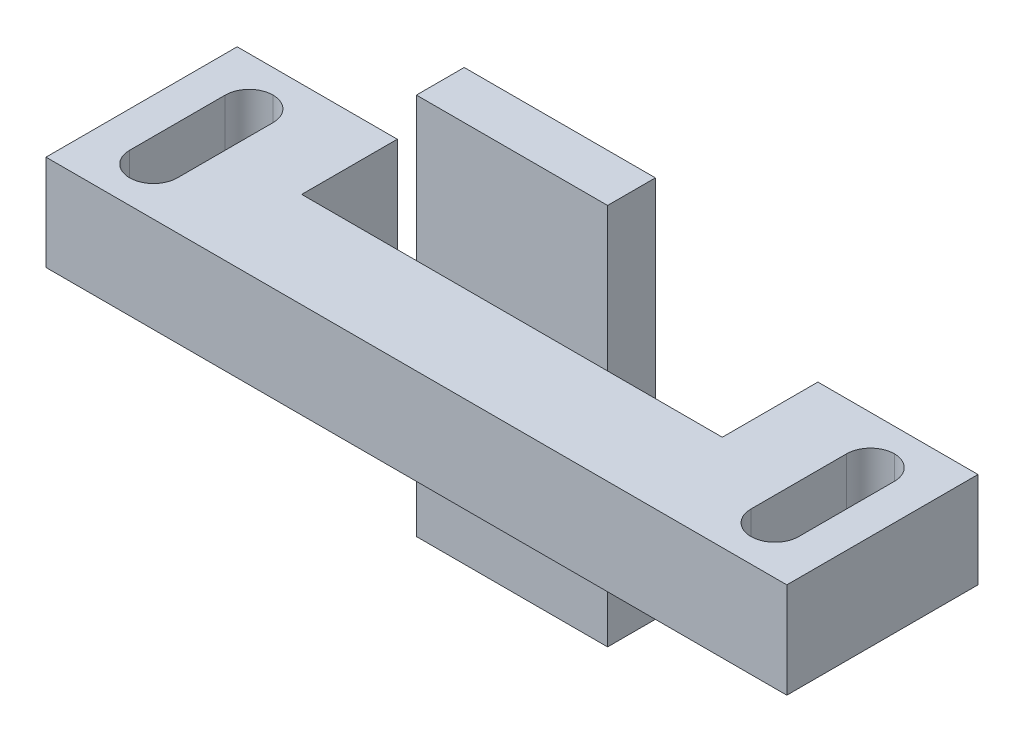
SolidWorks part; units mm, degrees
material "6061 Alloy"
ref_plane "Front Plane" through (0, 0, 0) normal (0, 0, 1) x (1, 0, 0)
ref_plane "Top Plane" through (0, 0, 0) normal (0, 1, 0) x (1, 0, 0)
ref_plane "Right Plane" through (0, 0, 0) normal (1, 0, 0) x (0, 0, -1)
sketch "Sketch1" plane through (0, 0, 0) normal (0, 0, 1) x (1, 0, 0)
  line L1 (-49.2125, 6.35) -> (49.2125, 6.35)
  line L2 (-49.2125, 6.35) -> (-49.2125, -6.35)
  line L3 (-49.2125, -6.35) -> (49.2125, -6.35)
  line L4 (49.2125, 6.35) -> (49.2125, -6.35)
  dimension "D1" = 49.2125
  dimension "D2" = 49.2125
  dimension "D3" = 6.35
  dimension "D4" = 6.35
extrude "Boss-Extrude1" add sketch "Sketch1" along normal mid plane 25.4
sketch "Sketch2" plane through (0, 6.35, 0) normal (0, 1, 0) x (1, 0, 0)
  line L1 (-44.45, 9.525) -> (-38.1, 9.525)
  line L2 (-44.45, 9.525) -> (-44.45, -9.525)
  line L3 (-44.45, -9.525) -> (-38.1, -9.525)
  line L4 (-38.1, 9.525) -> (-38.1, -9.525)
  line L5 (49.2125, 12.7) -> (-49.2125, 12.7) construction
  line L6 (49.2125, -12.7) -> (-49.2125, -12.7) construction
  dimension "D1" = 38.1
  dimension "D2" = 6.35
  dimension "D3" = 3.175
  dimension "D4" = 3.175
extrude "Cut-Extrude1" cut sketch "Sketch2" against normal up to next
fillet "Fillet1" radius 3.175 1 edges at (-44.45, 0, -9.525) type face fillet first side face at (-44.45, 0, 0) second side face at (-41.275, 0, -9.525)
fillet "Fillet2" radius 3.175 1 edges at (-38.1, 0, -9.525) type face fillet first side face at (-39.6875, 0, -9.525) second side face at (-38.1, 0, 0)
fillet "Fillet3" radius 3.175 1 edges at (-44.45, 0, 9.525) type face fillet first side face at (-44.45, 0, 1.5875) second side face at (-41.275, 0, 9.525)
fillet "Fillet4" radius 3.175 1 edges at (-38.1, 0, 9.525) type face fillet first side face at (-38.1, 0, 1.5875) second side face at (-39.6875, 0, 9.525)
mirror "Mirror1" about plane through (0, 0, 0) normal (1, 0, 0) of "Fillet4", "Fillet3", "Fillet2", "Fillet1", "Cut-Extrude1"
sketch "Sketch5" plane through (0, 6.35, 0) normal (0, 1, 0) x (1, 0, 0)
  line L0 (49.2125, 12.7) -> (-49.2125, 12.7) construction
  line L1 (-27.94, 12.7) -> (27.94, 12.7)
  line L2 (-27.94, 12.7) -> (-27.94, 0)
  line L3 (-27.94, 0) -> (27.94, 0)
  line L4 (27.94, 12.7) -> (27.94, 0)
  dimension "D1" = 12.7
  dimension "D2" = 27.94
  dimension "D3" = 27.94
extrude "Cut-Extrude2" cut sketch "Sketch5" against normal up to next
sketch "Sketch6" plane through (0, 0, 0) normal (0, 0, -1) x (-1, 0, 0)
  line L1 (-12.7, 25.4) -> (12.7, 25.4)
  line L2 (-12.7, 25.4) -> (-12.7, -25.4)
  line L3 (-12.7, -25.4) -> (12.7, -25.4)
  line L4 (12.7, 25.4) -> (12.7, -25.4)
  dimension "D1" = 12.7
  dimension "D2" = 12.7
  dimension "D3" = 25.4
  dimension "D4" = 25.4
extrude "Boss-Extrude3" add sketch "Sketch6" along normal blind 6.35
